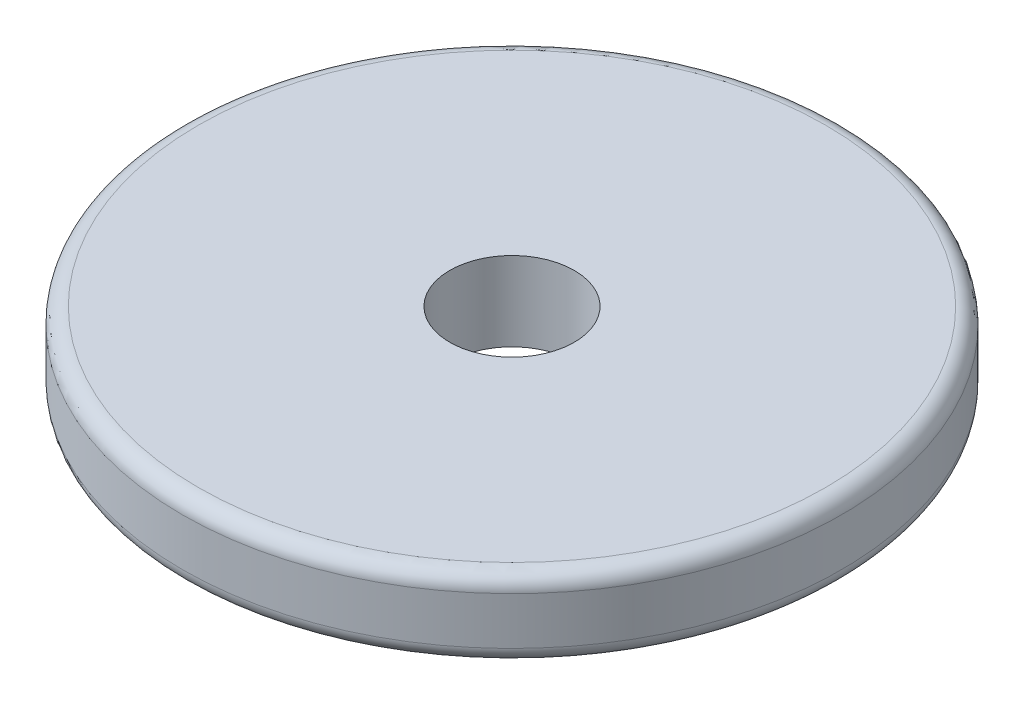
SolidWorks part; units mm, degrees
ref_plane "Front Plane" through (0, 0, 0) normal (0, 0, 1) x (1, 0, 0)
ref_plane "Top Plane" through (0, 0, 0) normal (0, 1, 0) x (1, 0, 0)
ref_plane "Right Plane" through (0, 0, 0) normal (1, 0, 0) x (0, 0, -1)
sketch "Sketch1" plane through (0, 0, 0) normal (0, 1, 0) x (1, 0, 0)
  circle A0 centre (0, 0) radius 15.875
  circle A1 centre (0, 0) radius 3
  dimension "D1" = 31.75
  dimension "D2" = 6
extrude "Boss-Extrude1" add sketch "Sketch1" along normal blind 3.81
fillet "Fillet1" radius 0.762 2 edges at (0, 0, 15.875) (0, 3.81, 15.875)
